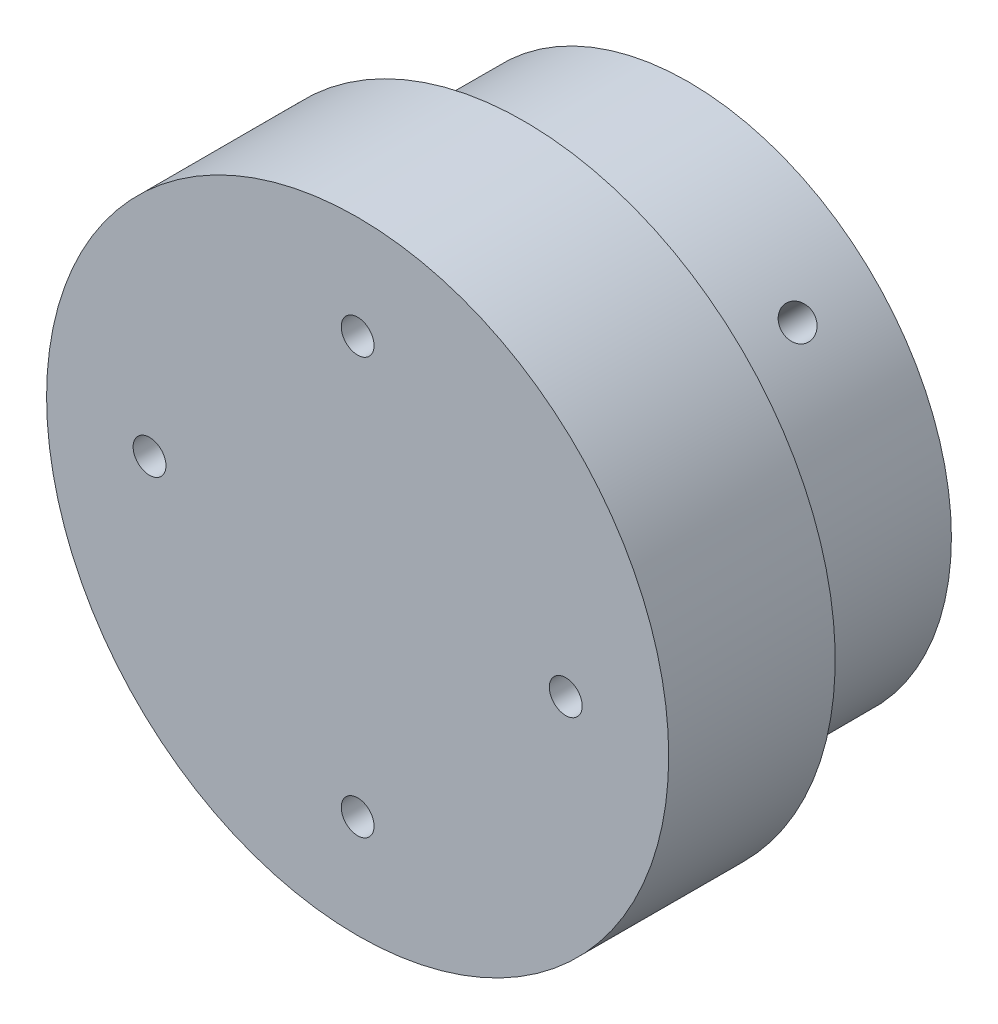
SolidWorks part; units mm, degrees
other "标注1"
sketch "草图12" plane through (37.5, 37.5, 0) normal (0.7889, 0.0518, -0.6123) x (-0.6143, 0.0411, -0.788)
ref_plane "前视基准面" through (0, 0, 0) normal (0, 0, 1) x (1, 0, 0)
ref_plane "上视基准面" through (0, 0, 0) normal (0, 1, 0) x (1, 0, 0)
ref_plane "右视基准面" through (0, 0, 0) normal (1, 0, 0) x (0, 0, -1)
other "Configuration Table"
sketch "草图1" plane through (0, 0, 0) normal (0, 0, 1) x (1, 0, 0)
  line L0 (-80.1161, 0) -> (76.2587, 0) construction
  line L1 (0, 70.3242) -> (0, -57.8617) construction
  circle A0 centre (0, 0) radius 37.5
extrude "凸台-拉伸1" add sketch "草图1" along normal blind 15.5 contours A0
sketch "草图2" plane through (0, 0, 0) normal (0, 0, -1) x (-1, 0, 0)
  line L0 (-35.6924, 0) -> (42.6192, 0) construction
  line L1 (0, 34.3455) -> (0, -34.6341) construction
  circle A0 centre (0, 0) radius 25 construction
  circle A1 centre (-25, 0) radius 3
  circle A2 centre (25, 0) radius 3
  circle A3 centre (0, 25) radius 3
  circle A4 centre (0, -25) radius 3
extrude "切除-拉伸1" cut sketch "草图2" against normal blind 16
sketch "草图4" plane through (0, 0, 15.5) normal (0, 0, 1) x (1, 0, 0)
  circle A0 centre (-25, 0) radius 4.8
  circle A1 centre (25, 0) radius 4.8
  circle A2 centre (0, 25) radius 4.8
  circle A3 centre (0, -25) radius 4.8
extrude "切除-拉伸2" cut sketch "草图4" against normal blind 4.5
sketch "草图6" plane through (0, 0, 15.5) normal (0, 0, 1) x (1, 0, 0)
  circle A0 centre (0, 0) radius 24.01
extrude "凸台-拉伸2" add sketch "草图6" along normal blind 23
sketch "草图7" plane through (0, 0, 38.5) normal (0, 0, 1) x (1, 0, 0)
  circle A0 centre (0, 0) radius 28.4
extrude "凸台-拉伸3" add sketch "草图7" along normal blind 14.2
sketch "草图5" plane through (0, 0, 52.7) normal (0, 0, 1) x (1, 0, 0)
  line L0 (29.1754, 0) -> (102.5005, 0) construction
  line L1 (0, 39.7422) -> (0, -41.002) construction
  circle A0 centre (0, 0) radius 19 construction
  circle A1 centre (-19, 0) radius 1.5
  circle A2 centre (19, 0) radius 1.5
  circle A3 centre (0, 19) radius 1.5
  circle A4 centre (0, -19) radius 1.5
extrude "切除-拉伸3" cut sketch "草图5" against normal blind 33
sketch "草图8" plane through (0, 0, 0) normal (0, 0, -1) x (-1, 0, 0)
  circle A0 centre (-19, 0) radius 2.75
  circle A1 centre (19, 0) radius 2.75
  circle A2 centre (0, 19) radius 2.75
  circle A3 centre (0, -19) radius 2.75
sketch "草图9" plane through (0, 0, 37.5) normal (0, 0, -1) x (-1, 0, 0)
  circle A0 centre (-19, 0) radius 2.75
  circle A1 centre (0, 19) radius 2.75
  circle A2 centre (19, 0) radius 2.75
  circle A3 centre (0, -19) radius 2.75
extrude "切除-拉伸6" cut sketch "草图9" along normal blind 58
sketch "草图10" plane through (0, 0, 37.5) normal (0, 0, -1) x (-1, 0, 0)
  arc A1 (-0.9277, -20.1787) -> (0.9277, -20.1787) centre (0, -19) ccw
  arc A2 (20.1787, -0.9277) -> (20.1787, 0.9277) centre (19, 0) ccw
  arc A3 (0.9277, 20.1787) -> (-0.9277, 20.1787) centre (0, 19) ccw
  arc A4 (-20.1787, 0.9277) -> (-20.1787, -0.9277) centre (-19, 0) ccw
  arc A5 (-0.9277, 20.1787) -> (-20.1787, 0.9277) centre (0, 0) ccw
  arc A6 (20.1787, 0.9277) -> (0.9277, 20.1787) centre (0, 0) ccw
  arc A7 (-20.1787, -0.9277) -> (-0.9277, -20.1787) centre (0, 0) ccw
  arc A8 (0.9277, -20.1787) -> (20.1787, -0.9277) centre (0, 0) ccw
  circle A9 centre (0, 0) radius 28.4
extrude "凸台-拉伸5" add sketch "草图10" against normal blind 1
sketch "草图11" plane through (0, 0, 37.5) normal (0, 0, -1) x (-1, 0, 0)
  circle A0 centre (0, 19) radius 4
  circle A1 centre (-19, 0) radius 4
  circle A2 centre (19, 0) radius 4
  circle A3 centre (0, -19) radius 4
extrude "切除-拉伸7" cut sketch "草图11" along normal blind 22
sketch "草图13" plane through (0, 0, 0) normal (0, 1, 0) x (1, 0, 0)
  line L2 (-52.2125, -22.5) -> (-52.2125, 12.6202)
  line L3 (-52.2125, 12.6202) -> (47.7984, 12.6202)
  line L4 (47.7984, 12.6202) -> (47.7984, -22.5)
  line L7 (0, -22.5) -> (-52.2125, -22.5)
  line L8 (0, -22.5) -> (47.7984, -22.5)
  point P0 (0, 0)
extrude "切除-拉伸9" cut sketch "草图13" against normal blind 74 and the other way blind 74
ref_plane "基准面1" through (24.01, 0, 0) normal (1, 0, 0) x (0, 0, -1)
ref_plane "基准面2" through (0, 24.01, 0) normal (0, 1, 0) x (1, 0, 0)
ref_plane "基准面3" through (0, 0, 0) normal (-0.7071, 0.7071, 0) x (0.7071, 0.7071, 0)
ref_plane "基准面4" through (-16.9776, 16.9776, 0) normal (-0.7071, 0.7071, 0) x (0.7071, 0.7071, 0)
ref_plane "基准面5" through (16.9776, -16.9776, 0) normal (-0.7071, 0.7071, 0) x (0.7071, 0.7071, 0)
sketch "草图15" plane through (16.9776, -16.9776, 0) normal (-0.7071, 0.7071, 0) x (0.7071, 0.7071, 0)
  circle A0 centre (0, -29.5) radius 1.45
extrude "切除-拉伸10" cut sketch "草图15" along normal blind 74
ref_plane "基准面7" through (-16.9776, -16.9776, 0) normal (-0.7071, -0.7071, 0) x (0, 0, 1)
sketch "草图16" plane through (-16.9776, -16.9776, 0) normal (-0.7071, -0.7071, 0) x (0, 0, 1)
  line L2 (55, 0) -> (-55, 0) construction
  circle A0 centre (29.5, 0) radius 1.45
extrude "切除-拉伸11" cut sketch "草图16" against normal blind 74
